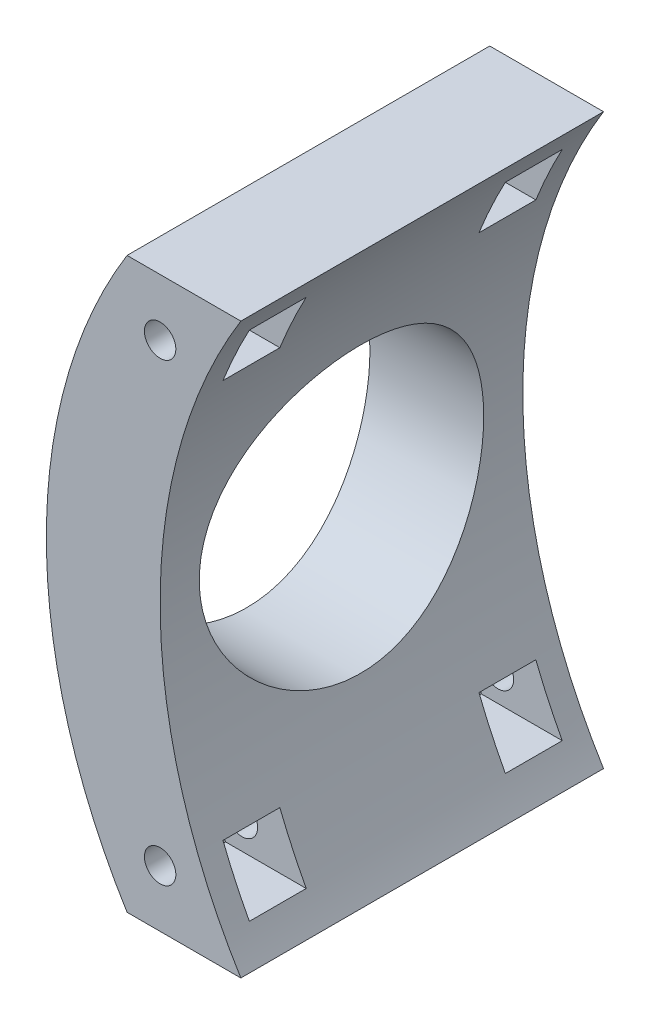
SolidWorks part; units mm, degrees
material "CA"
ref_plane "Front Plane" through (0, 0, 0) normal (0, 0, 1) x (1, 0, 0)
ref_plane "Top Plane" through (0, 0, 0) normal (0, 1, 0) x (1, 0, 0)
ref_plane "Right Plane" through (0, 0, 0) normal (1, 0, 0) x (0, 0, -1)
sketch "Sketch1" plane through (0, 0, 0) normal (0, 0, 1) x (1, 0, 0)
  line L0 (0, -31.75) -> (0, 31.75) construction
  line L1 (0, 31.75) -> (12.7, 31.75)
  line L3 (12.7, -31.75) -> (0, -31.75)
  arc A0 (0, 31.75) -> (0, -31.75) centre (51.443, 0) ccw
  circle A1 centre (3.691, 25.4) radius 1.7526
  circle A2 centre (3.691, -25.4) radius 1.7526
  arc A3 (12.7, 31.75) -> (12.7, -31.75) centre (64.143, 0) ccw
  point P4 (0, 0)
  point P13 (3.691, 0)
  point P15 (-9.009, 0)
  dimension "D2" = 60.452
  dimension "D3" = 3.5052
  dimension "D1" = 63.5
  dimension "D4" = 50.8
  dimension "D5" = 6.35
  dimension "D6" = 12.7
  dimension "D7" = 12.7
extrude "Boss-Extrude1" add sketch "Sketch1" along normal mid plane 40.4812
sketch "Sketch2" plane through (0, 0, 0) normal (0, 0, 1) x (1, 0, 0)
  line L1 (21.8516, 28.575) -> (1.8579, 28.575)
  line L2 (1.8579, 28.575) -> (0.0248, 25.4)
  line L3 (0.0248, 25.4) -> (1.8579, 22.225)
  line L4 (1.8579, 22.225) -> (21.8516, 22.225)
  line L7 (21.8516, 28.575) -> (21.8516, 22.225)
  line L9 (0, 0) -> (45.3612, 0) construction
  line L10 (7.3572, 25.4) -> (6.4406, 26.9875) [skipped]
  line L11 (5.5241, 22.225) -> (6.4406, 23.8125) [skipped]
  line L12 (21.8516, -28.575) -> (21.8516, -22.225)
  line L13 (1.8579, -22.225) -> (21.8516, -22.225)
  line L14 (0.0248, -25.4) -> (1.8579, -22.225)
  line L15 (1.8579, -28.575) -> (0.0248, -25.4)
  line L16 (21.8516, -28.575) -> (1.8579, -28.575)
  circle A0 centre (3.691, 25.4) radius 3.175 construction
  point P0 (3.691, 25.4)
  dimension "D1" = 6.35
extrude "Cut-Extrude1" cut sketch "Sketch2" against normal blind 6.35 from offset 17.4625
extrude "Cut-Extrude2" cut sketch "Sketch2<2>" along normal blind 6.35 from offset 17.4625 offset against normal yes
sketch "Sketch2<2>" plane through (0, 0, 0) normal (0, 0, 1) x (1, 0, 0) same geometry as "Sketch2"
sketch "Sketch4" plane through (0, 0, 0) normal (1, 0, 0) x (0, 0, -1)
  circle A0 centre (0, 0) radius 15.875
  dimension "D1" = 31.75
extrude "Cut-Extrude3" cut sketch "Sketch4" against normal through all both and the other way through all
